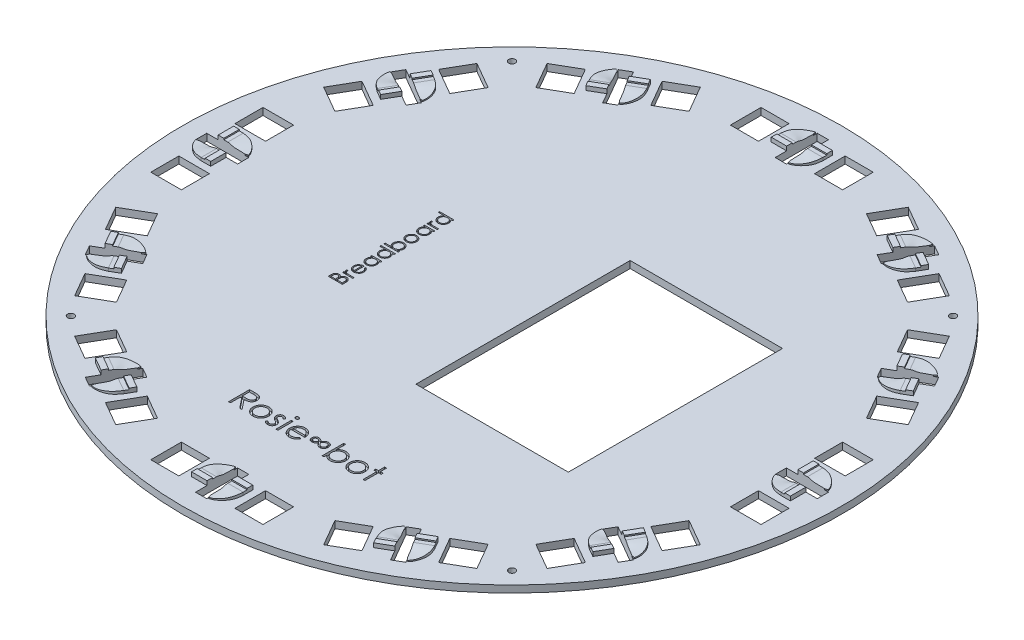
SolidWorks part; units mm, degrees
ref_plane "Front" through (0, 0, 0) normal (0, 0, 1) x (1, 0, 0)
ref_plane "Top" through (0, 0, 0) normal (0, 1, 0) x (1, 0, 0)
ref_plane "Right" through (0, 0, 0) normal (1, 0, 0) x (0, 0, -1)
sketch "Sketch1" plane through (0, 0, 0) normal (0, 1, 0) x (1, 0, 0)
  circle A0 centre (0, 0) radius 149.225
  dimension "D1" = 298.45
extrude "Base" add sketch "Sketch1" along normal blind 3.175 contours A0
sketch "Sketch2" plane through (0, 3.175, 0) normal (0, 1, 0) x (1, 0, 0)
  line L1 (-2.54, -140.758) -> (2.54, -140.758)
  line L2 (-2.54, -140.758) -> (-2.54, -121.708)
  line L3 (-2.54, -121.708) -> (2.54, -121.708)
  line L4 (2.54, -140.758) -> (2.54, -121.708)
  circle A0 centre (0, 0) radius 149.225 construction
  point P4 (0, -121.708)
  dimension "D1" = 5.08
  dimension "D2" = 19.05
  dimension "D3" = 140.758
extrude "Cut-Extrude1" cut sketch "Sketch2" against normal up to next and the other way through all contours L1 L4 L3 L2
sketch "Sketch4" plane through (0, 3.175, 0) normal (0, 1, 0) x (1, 0, 0)
  line L0 (0, -131.233) -> (-2.9434, -122.1742) construction
  line L1 (-2.9434, -122.1742) -> (0, -131.233) construction
  line L2 (0, -131.233) -> (-5.5987, -123.5271) construction
  line L3 (0, -131.233) -> (-7.7059, -125.6343) construction
  line L4 (0, -131.233) -> (-9.0588, -128.2896) construction
  line L5 (0, -131.233) -> (-9.525, -131.233) construction
  line L9 (2.54, -121.708) -> (-2.54, -121.708) construction
  line L10 (2.54, -121.708) -> (2.54, -140.758) construction
  line L11 (-2.54, -121.708) -> (-2.54, -140.758) construction
  line L12 (2.54, -140.758) -> (-2.54, -140.758) construction
  circle A0 centre (0, -131.233) radius 9.525 construction
  point P16 (0, -121.708)
  point P19 (2.54, -131.233)
  dimension "D1" = 18
  dimension "D2" = 18
  dimension "D3" = 18
  dimension "D4" = 18
  dimension "D5" = 18
ref_plane "Plane1" through (-38.5684, 0, 12.5316) normal (0.9511, 0, -0.309) x (-0.309, 0, -0.9511)
ref_plane "Plane2" through (-62.405, 0, 45.3399) normal (0.809, 0, -0.5878) x (-0.5878, 0, -0.809)
ref_plane "Plane3" through (-62.405, 0, 85.8931) normal (0.5878, 0, -0.809) x (-0.809, 0, -0.5878)
ref_plane "Plane4" through (-38.5684, 0, 118.7014) normal (0.309, 0, -0.9511) x (-0.9511, 0, -0.309)
ref_plane "Plane5" through (0, 0, 131.233) normal (0, 0, -1) x (-1, 0, 0)
sketch "Sketch5" plane through (-38.5684, 0, 12.5316) normal (0.9511, 0, -0.309) x (-0.309, 0, -0.9511)
  line L0 (-114.9663, 3.175) -> (-133.0839, 3.175) construction
  line L1 (-116.5904, 3.175) -> (-115.285, 3.175)
  line L2 (-116.5904, 3.175) -> (-116.5904, 3.683)
  line L3 (-116.5904, 3.683) -> (-115.285, 3.683)
  line L4 (-115.285, 3.175) -> (-115.285, 3.683)
  dimension "D2" = 0.508
sketch "Sketch6" plane through (-62.405, 0, 45.3399) normal (0.809, 0, -0.5878) x (-0.5878, 0, -0.809)
  line L0 (-96.9709, 3.175) -> (-112.3826, 3.175) construction
  line L1 (-101.8484, 3.175) -> (-96.6447, 3.175)
  line L2 (-101.8484, 3.175) -> (-101.8484, 3.775)
  line L3 (-101.8484, 3.775) -> (-96.6447, 3.775)
  line L4 (-96.6447, 3.175) -> (-96.6447, 3.775)
  dimension "D2" = 0.6
sketch "Sketch7" plane through (-62.405, 0, 85.8931) normal (0.5878, 0, -0.809) x (-0.809, 0, -0.5878)
  line L0 (-69.4833, 3.175) -> (-80.6806, 3.175) construction
  line L1 (-73.9972, 3.175) -> (-67.6118, 3.175)
  line L2 (-73.9972, 3.175) -> (-73.9972, 4.075)
  line L3 (-73.9972, 4.075) -> (-67.6118, 4.075)
  line L4 (-67.6118, 3.175) -> (-67.6118, 4.075)
  dimension "D2" = 0.9
sketch "Sketch10" plane through (-38.5684, 0, 118.7014) normal (0.309, 0, -0.9511) x (-0.9511, 0, -0.309)
  line L0 (-40.5532, 3.175) -> (-31.4944, 3.175) construction
  line L1 (-37.8825, 3.175) -> (-31.0282, 3.175)
  line L2 (-37.8825, 3.175) -> (-37.8825, 4.375)
  line L3 (-37.8825, 4.375) -> (-31.0282, 4.375)
  line L4 (-31.0282, 3.175) -> (-31.0282, 4.375)
  dimension "D3" = 1.2
sketch "Sketch11" plane through (0, 0, 131.233) normal (0, 0, -1) x (-1, 0, 0)
  line L0 (0, 3.175) -> (9.525, 3.175) construction
  line L1 (2.54, 3.175) -> (9.525, 3.175)
  line L2 (2.54, 3.175) -> (2.54, 4.475)
  line L3 (2.54, 4.475) -> (9.525, 4.475)
  line L4 (9.525, 3.175) -> (9.525, 4.475)
  dimension "D3" = 1.3
loft "Loft1" add profiles "Sketch5", "Sketch6", "Sketch7", "Sketch10", "Sketch11" connector at (-2.54, 3.683, 123.4157) connector at (-2.54, 3.775, 127.737) connector at (-2.54, 4.075, 129.3876) connector at (-2.54, 4.375, 130.4077) connector at (-2.54, 4.475, 131.233)
sketch "Sketch13" plane through (-104.9799, 0, 131.233) normal (0, 0, -1) x (-1, 0, 0)
  line L6 (-95.4549, 3.175) -> (-102.4399, 3.175)
  line L7 (-95.4549, 3.175) -> (-95.4549, 4.475)
  line L8 (-95.4549, 4.475) -> (-102.4399, 4.475)
  line L9 (-102.4399, 3.175) -> (-102.4399, 4.475)
extrude "Boss-Extrude4" add sketch "Sketch13" against normal blind 1.7907
sketch "Sketch25" plane through (0, 0, 133.0237) normal (0, 0, 1) x (1, 0, 0)
  line L0 (-9.525, 4.475) -> (-2.54, 4.475) construction
  line L1 (-9.525, 3.175) -> (-2.54, 3.175)
  line L2 (-9.525, 3.175) -> (-9.525, 5.075)
  line L3 (-9.525, 5.075) -> (-2.54, 5.075)
  line L4 (-2.54, 3.175) -> (-2.54, 5.075)
  dimension "D1" = 0.6
extrude "Boss-Extrude5" add sketch "Sketch25" along normal blind 2.54
sketch "Sketch14" plane through (-2.54, 0, 0) normal (1, 0, 0) x (0, 0, -1)
  line L0 (-131.233, 3.175) -> (-131.233, 0) construction
  line L1 (-121.708, 0) -> (-140.758, 0) construction
ref_plane "Plane6" through (0, 0, 0) normal (1, 0, 0) x (0, 0, -1)
sketch "Sketch15" plane through (0, 0, 0) normal (1, 0, 0) x (0, 0, -1)
  line L0 (-131.233, 0) -> (-131.233, 3.175) construction
pattern_circular "CirPattern1" count 2 over 360 about axis through (0, 0, 131.233) along (0, 1, 0) of "Loft1", "Boss-Extrude5", "Boss-Extrude4" reverse direction yes
ref_axis "Axis1" through (0, 50, 0) along (0, -1, 0)
pattern_circular "Full_Spiral_Pattern" count 12 over 360 about axis through (0, 50, 0) along (0, -1, 0) of "CirPattern1", "Cut-Extrude1"
sketch "Sketch18" plane through (0, 3.175, 0) normal (0, 1, 0) x (1, 0, 0)
  line L0 (12.7, 40.64) -> (60.96, 40.64) construction
  line L1 (12.7, 40.64) -> (12.7, -40.64) construction
  line L2 (60.96, -34.29) -> (12.7, -34.29) construction
  line L3 (60.96, -34.29) -> (60.96, 40.64) construction
  line L4 (0, -149.225) -> (0, 149.225) construction
  line L5 (0, -1.7463) -> (0, 1.7463) construction
  line L6 (-149.225, 0) -> (149.225, 0) construction
  line L7 (12.7, 41.91) -> (12.7, 40.64) construction
  circle A0 centre (12.7, 41.91) radius 2.77
  circle A1 centre (12.7, -40.64) radius 2.77
  circle A2 centre (60.96, -34.29) radius 2.77
  circle A3 centre (60.96, 40.64) radius 2.77
  circle A4 centre (12.7, -40.64) radius 1.5
  circle A5 centre (12.7, 41.91) radius 1.5
  circle A6 centre (60.96, 40.64) radius 1.5
  circle A7 centre (60.96, -34.29) radius 1.5
  circle A8 centre (0, 0) radius 149.225 construction
  point P22 (12.7, 0)
  dimension "D7" = 12.7
  dimension "D5" = 3
  dimension "D6" = 1.27
  dimension "D1" = 82.55
  dimension "D2" = 74.93
  dimension "D3" = 48.26
  dimension "D4" = 1.27
sketch "Sketch19" plane through (0, 3.175, 0) normal (0, 1, 0) x (1, 0, 0)
  line L0 (-99.8612, -99.8612) -> (0, 0) construction
  line L1 (0, -149.225) -> (0, 149.225) construction
  circle A1 centre (-99.8612, -99.8612) radius 1.5
  dimension "D4" = 3
  dimension "D5" = 45
  dimension "D1" = 141.225
extrude "Cut-Extrude2" cut sketch "Sketch19" against normal through all
pattern_circular "CirPattern7" count 4 over 360 about axis through (0, 50, 0) along (0, -1, 0) of "Cut-Extrude2"
extrude "MegaScrews" add sketch "Sketch18" along normal blind 3.81
sketch "Sketch23" plane through (0, 3.175, 0) normal (0, 1, 0) x (1, 0, 0)
  line L9 (-2.54, -135.5637) -> (-2.54, -140.758) construction
  line L10 (-25.4, -124.3051) -> (-12.7, -124.3051)
  line L11 (-25.4, -124.3051) -> (-25.4, -138.1608)
  line L16 (-25.4, -138.1608) -> (-12.7, -138.1608)
  line L17 (-12.7, -124.3051) -> (-12.7, -138.1608)
  line L19 (2.54, -121.708) -> (2.54, -126.9023) construction
  line L20 (0, -50) -> (0, 50) construction
  line L21 (12.7, -124.3051) -> (12.7, -138.1608)
  line L22 (25.4, -138.1608) -> (12.7, -138.1608)
  line L23 (25.4, -124.3051) -> (25.4, -138.1608)
  line L24 (25.4, -124.3051) -> (12.7, -124.3051)
  point P8 (-2.54, -138.1608)
  point P9 (2.54, -124.3051)
  dimension "D1" = 12.7
  dimension "D2" = 10.16
extrude "Cut-Extrude6" cut sketch "Sketch23" against normal through all
pattern_circular "CirPattern8" count 12 over 360 about axis through (0, 50, 0) along (0, -1, 0) of "Cut-Extrude6"
sketch "Sketch17" plane through (0, 3.175, 0) normal (0, 1, 0) x (1, 0, 0)
  line L0 (-31.75, -97.8162) -> (31.75, -97.8162) construction
  point P3 (0, -97.8162)
  dimension "D2" = 97.8162
  dimension "D1" = 63.5
sketch "Sketch16" plane through (0, 3.175, 0) normal (0, 1, 0) x (1, 0, 0)
  line L0 (-31.75, -97.8162) -> (31.75, -97.8162) construction
  text T0 "Rosie∞bot\r\n" font "Century Gothic" height in points 36
extrude "Cut-Extrude4" cut sketch "Sketch16" against normal blind 1.27
sketch "Sketch22" plane through (0, 3.175, 0) normal (0, 1, 0) x (1, 0, 0)
  line L0 (-50.8, 25.1735) -> (-50.8, -31.2294) construction
  text T0 "Breadboard"
  dimension "D1" = 50.8
extrude "Cut-Extrude5" cut sketch "Sketch22" against normal blind 1.27
sketch "Sketch24" plane through (0, 3.175, 0) normal (0, 1, 0) x (1, 0, 0)
  line L0 (35.4114, -12.631) -> (36.0762, 12.631) construction
  circle A0 centre (12.7, 41.91) radius 1.5 construction
  circle A1 centre (60.96, 40.64) radius 1.5 construction
  text T0 "Mega"
  point P12 (35.7438, 0)
extrude "Cut-Extrude7" cut sketch "Sketch24" against normal blind 1.27
sketch "Sketch26" plane through (0, 3.175, 0) normal (0, 1, 0) x (1, 0, 0)
  line L1 (5, -48.5) -> (74, -48.5)
  line L2 (5, -48.5) -> (5, 48.5)
  line L3 (5, 48.5) -> (74, 48.5)
  line L4 (74, -48.5) -> (74, 48.5)
  point P4 (5, 0)
  dimension "D1" = 69
  dimension "D2" = 97
  dimension "D3" = 5
extrude "Cut-Extrude8" cut sketch "Sketch26" against normal through all
equation "\"Diameter_Daisy\"= 11.75in'Outside diameter of base"
equation "\"D1@Sketch1\"=\"Diameter_Daisy\""
equation "\"D3@Sketch2\"=\"Diameter_Daisy\"/2-8.467mm"
equation "\"D1@Sketch19\"=\"Diameter_Daisy\"/2-8mm"
equation "\"Number_of_Holes\" = 12"
equation "\"D5@Sketch19\"=360/\"Number_of_Holes\"/2*3"
equation "\"D1@Full_Spiral_Pattern\"=\"Number_of_Holes\""
equation "\"D1@CirPattern8\"=\"Number_of_Holes\""
